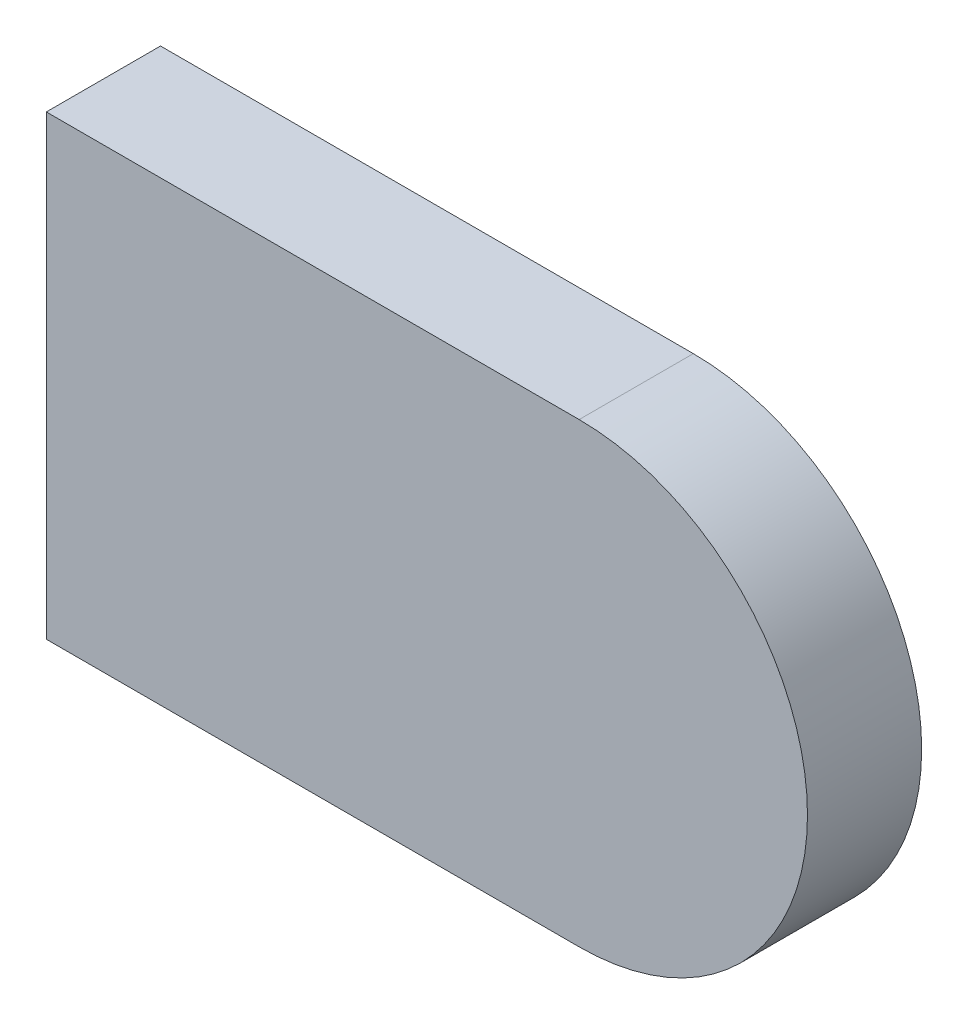
SolidWorks part; units mm, degrees
ref_plane "Front" through (0, 0, 0) normal (0, 0, 1) x (1, 0, 0)
ref_plane "Top" through (0, 0, 0) normal (0, 1, 0) x (1, 0, 0)
ref_plane "Right" through (0, 0, 0) normal (1, 0, 0) x (0, 0, -1)
sketch "Sketch1" plane through (0, 0, 0) normal (0, 0, 1) x (1, 0, 0)
  line L1 (0, 0) -> (88.9034, 0)
  line L2 (0, 0) -> (0, 76.2)
  line L3 (0, 76.2) -> (88.9, 76.2)
  arc A0 (88.9, 76.2) -> (126.9966, 38.0942) centre (88.8966, 38.1) cw
  arc A1 (126.9966, 38.0942) -> (88.9034, 0) centre (88.8966, 38.1) cw
  dimension "D5" = 38.1
  dimension "D3" = 38.1
  dimension "D1" = 88.9
  dimension "D2" = 88.9034
  dimension "D4" = 76.2
  dimension "D6" = 38.1
extrude "Boss-Extrude1" add sketch "Sketch1" along normal blind 19.05
sketch "Sketch3" plane through (0, 0, 0) normal (-1, 0, 0) x (0, 0, 1)
  line L0 (0, 76.2) -> (19.05, 0) construction
  line L1 (19.05, 76.2) -> (0, 0) construction
  circle A0 centre (9.525, 38.1) radius 6.35
  dimension "D1" = 12.7
extrude "Cut-Extrude1" cut sketch "Sketch3" against normal blind 25.4 contours A0
